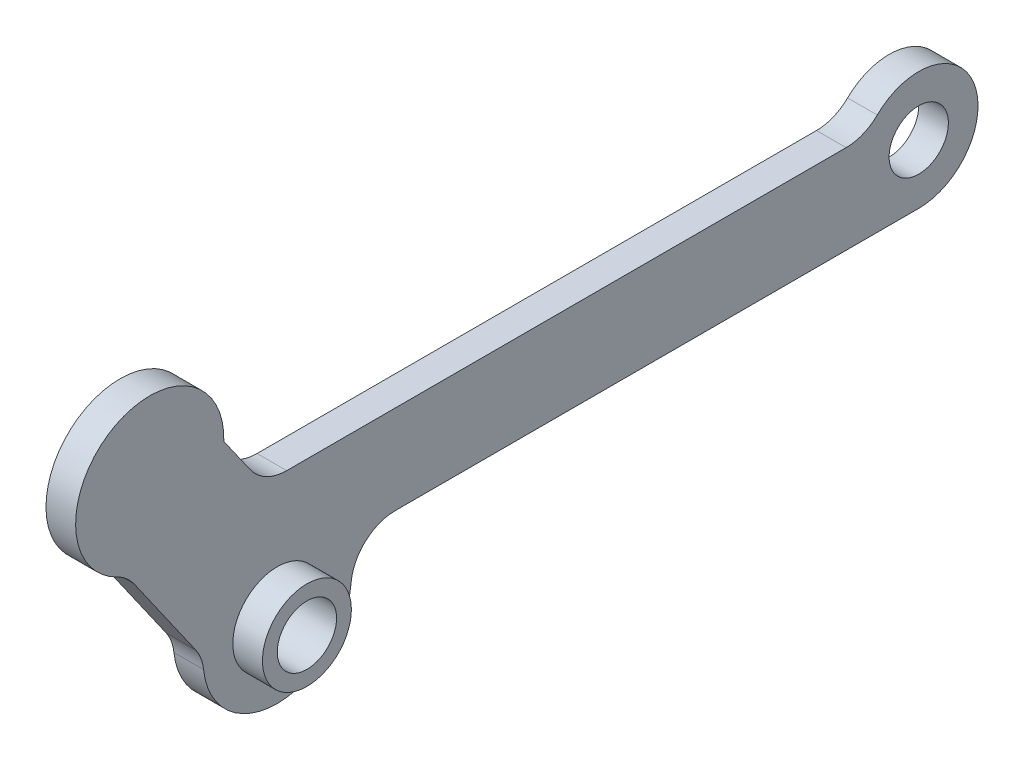
SolidWorks part; units mm, degrees
ref_plane "前视基准面" through (0, 0, 0) normal (0, 0, 1) x (1, 0, 0)
ref_plane "上视基准面" through (0, 0, 0) normal (0, 1, 0) x (1, 0, 0)
ref_plane "右视基准面" through (0, 0, 0) normal (1, 0, 0) x (0, 0, -1)
other "Configuration Table"
sketch "草图1" plane through (0, 0, 0) normal (1, 0, 0) x (0, 0, -1)
  line L1 (0, 0) -> (44.2012, 0)
  line L2 (0, 0) -> (4.2012, -6)
  line L3 (4.2012, -6) -> (44.2012, -6)
  line L4 (44.2012, 0) -> (44.2012, -6)
  line L5 (-10.9556, 1.6987) -> (-4.4024, 6.2873)
  line L6 (-10.9556, 1.6987) -> (-2.352, -10.5886)
  line L7 (-2.352, -10.5886) -> (4.2012, -6)
  line L8 (-4.4024, 6.2873) -> (4.2012, -6)
  circle A0 centre (-7.679, 3.993) radius 5
  circle A1 centre (0.9246, -8.2943) radius 5
  circle A3 centre (44.2012, -2) radius 4
  circle A4 centre (-7.679, 3.993) radius 2
  circle A5 centre (44.2012, -2) radius 2
  circle A6 centre (0.9246, -8.2943) radius 2
  circle A7 centre (0.9246, -8.2943) radius 3
  dimension "D5" = 10
  dimension "D6" = 10
  dimension "D8" = 8
  dimension "D9" = 4
  dimension "D10" = 6
  dimension "D1" = 125
  dimension "D2" = 40
  dimension "D3" = 6
  dimension "D4" = 8
  dimension "D7" = 15
extrude "凸台-拉伸1" add sketch "草图1" along normal blind 2 contours A3 L1 L2 A1 L3 | A0 | L8 L5 L6 L7 | A1 | A3 region at (0, -2.9524, -21.636)
extrude "凸台-拉伸2" add sketch "草图1<4>" along normal blind 2 from surface contours A7 starting at face at (2, -1.9447, -10.9003)
sketch "草图1<4>" plane through (0, 0, 0) normal (1, 0, 0) x (0, 0, -1) same geometry as "草图1"
extrude "切除-拉伸1" cut sketch "草图1<3>" along normal through all both and the other way through all contours A4 | A6 | A5
sketch "草图1<3>" plane through (0, 0, 0) normal (1, 0, 0) x (0, 0, -1) same geometry as "草图1"
fillet "圆角1" radius 3 5 edges at (1, 0, -40.7371) (1, -8.1312, 4.0727) (1, -0.7588, 9.2349) (1, -6, -5.3672) (1, 0, 0)
sketch "草图2" plane through (0, 0, 0) normal (-1, 0, 0) x (0, 0, 1)
  circle A0 centre (7.679, 3.993) radius 2
  circle A1 centre (7.679, 3.993) radius 1.8
  circle A2 centre (7.679, 3.993) radius 2 construction
  dimension "D1" = 3.6
extrude "凸台-拉伸3" add sketch "草图2" against normal up to surface (2 mm away) contours A0 up to face at (2, 3.993, 5.679)
extrude "凸台-拉伸4" add sketch "草图2<3>" along normal blind 2 contours A1 region at (0, 3.993, 7.679)
sketch "草图2<3>" plane through (0, 0, 0) normal (-1, 0, 0) x (0, 0, 1) same geometry as "草图2"
